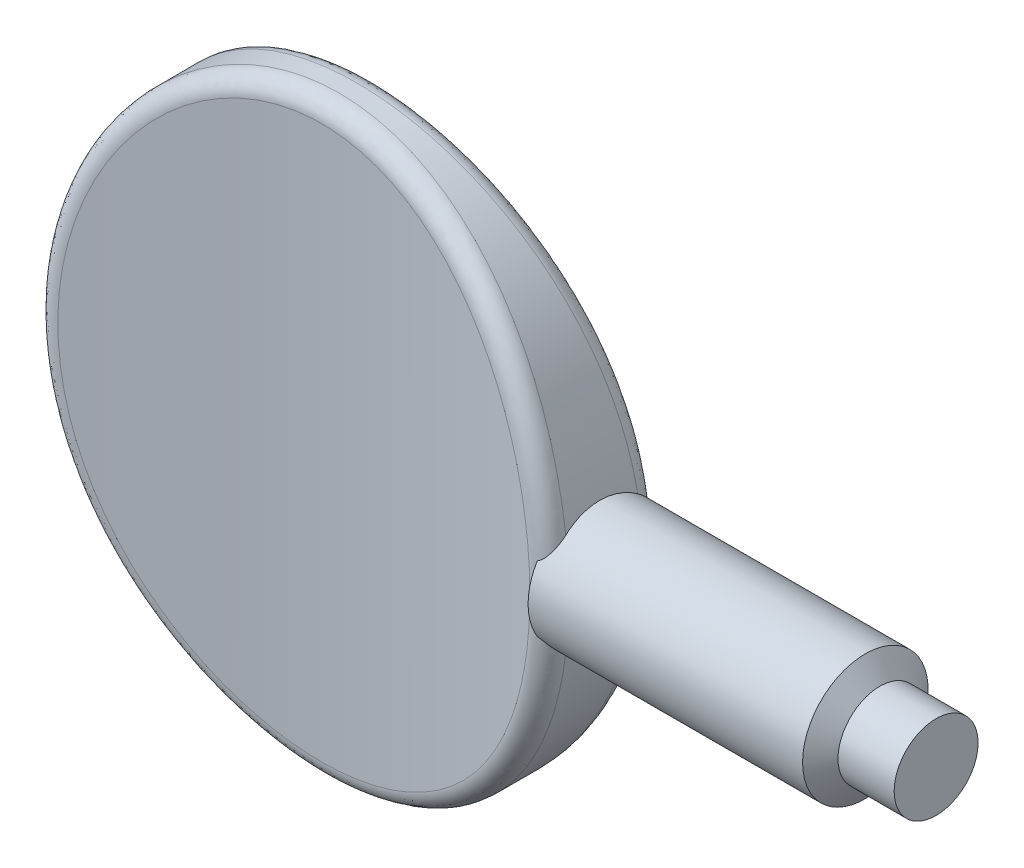
SolidWorks part; units mm, degrees
ref_plane "Front" through (0, 0, 0) normal (0, 0, 1) x (1, 0, 0)
ref_plane "Top" through (0, 0, 0) normal (0, 1, 0) x (1, 0, 0)
ref_plane "Right" through (0, 0, 0) normal (1, 0, 0) x (0, 0, -1)
ref_axis "Axis1" through (-50, 0, 0) along (1, 0, 0)
sketch "Sketch1" plane through (0, 0, 0) normal (0, 0, 1) x (1, 0, 0)
  line L0 (0, 0) -> (22.606, 0) construction
  line L1 (13.208, -2.413) -> (13.208, 2.413)
  line L2 (13.208, -2.413) -> (9.6776, -2.413) construction
  ellipse E0 centre (0, 0) end of major axis (0, -11.303) minor radius 9.906
  dimension "D2" = 3.302
  dimension "B" = 19.812
  dimension "L" = 12.7
extrude "Extrude1" add sketch "Sketch1" along normal mid plane 4.572
sketch "Sketch2" plane through (0, 0, 0) normal (0, 1, 0) x (1, 0, 0)
  line L0 (9.906, 2.286) -> (-9.906, 2.286) construction
  line L1 (0, 0) -> (0, 1.1721) construction
  line L2 (-1.7991, 0) -> (2.0444, 0) construction
  line L3 (-9.906, -2.286) -> (9.906, -2.286) construction
  line L6 (-9.906, 2.286) -> (-9.906, -2.286)
  line L7 (9.906, 2.286) -> (9.906, -2.286)
  arc A0 (-9.906, 2.286) -> (9.906, 2.286) centre (0, 40.2844) ccw
  arc A1 (-9.906, -2.286) -> (9.906, -2.286) centre (0, -40.2844) cw
extrude "Cut-Extrude1" cut sketch "Sketch2" against normal through all and the other way through all flip side to cut
fillet "Fillet3" radius 0.6773 2 edges at (-9.9037, -0.2444, 2.2854) (2.9825, 10.7785, -1.1294)
sketch "Sketch3" plane through (0, 0, 0) normal (0, 1, 0) x (1, 0, 0)
  line L0 (22.606, 0) -> (22.606, 1.6129)
  line L1 (0, 0) -> (17.8703, 0) construction
  line L2 (0, 0) -> (22.606, 0) construction
  line L3 (13.208, 2.413) -> (13.208, 0) construction
  line L4 (13.208, 2.413) -> (19.8868, 2.413)
  line L5 (22.606, 1.6129) -> (20.447, 1.6129)
  line L6 (13.208, 2.413) -> (9.3367, 2.413)
  line L7 (9.0722, 2.0783) -> (9.0722, 0)
  line L8 (9.3367, 0) -> (9.3367, 2.413) construction
  line L9 (9.0722, 0) -> (22.606, 0)
  line L10 (20.447, 1.6129) -> (19.8868, 2.413)
  arc A0 (9.3367, 2.413) -> (9.0722, 2.0783) centre (8.9927, 2.413) cw
  arc A3 (-9.906, 2.286) -> (9.906, 2.286) centre (0, 40.2844) ccw construction
  dimension "D1" = 35
revolve "Revolve1" add sketch "Sketch3" angle 360 about L0
cosmetic thread "Cosmetic Thread1" [suppressed]
sketch "Sketch4" plane through (0, 0, 0) normal (0, 0, 1) x (1, 0, 0)
  line L0 (0, 0) -> (27.7993, 0) construction
  line L1 (19.7035, 2.413) -> (19.8868, 2.0955)
  line L2 (19.8868, 2.0955) -> (20.0701, 2.413)
  line L3 (20.0701, 2.413) -> (20.0701, 2.7796)
  line L4 (20.0701, 2.7796) -> (19.7035, 2.7796)
  line L5 (19.7035, 2.7796) -> (19.7035, 2.413)
  line L6 (19.8868, 2.413) -> (19.8868, -2.413) construction
  dimension "D1" = 4.191
  dimension "D2" = 4.826
revolve "Cut-Revolve10" [suppressed] cut sketch "Sketch4" angle 360 about L0
pattern_linear "LPattern10" [suppressed] count 19 along (-1, 0, 0) of bodies 109
equation "\"D2@Sketch1\" = \"B@Sketch1\" / 6"
equation "\"D1@Fillet3\" = \"C1@Sketch2\" / 3"
equation "\"DIA@Sketch3\" = \"D@Sketch1\""
equation "\"D1@Cosmetic Thread1\" = \"L@Sketch1\" - \"Q@Sketch3\" -  ( \"D@Sketch1\" - \"P@Sketch3\" )  / 1.733"
equation "\"D1@Sketch4\" = \"D2@Cosmetic Thread1\""
equation "\"D2@Sketch4\" = \"DIA@Sketch3\""
equation "\"D1@LPattern10\" = \"D1@Cosmetic Thread1\" / \"P@LPattern10\" "
